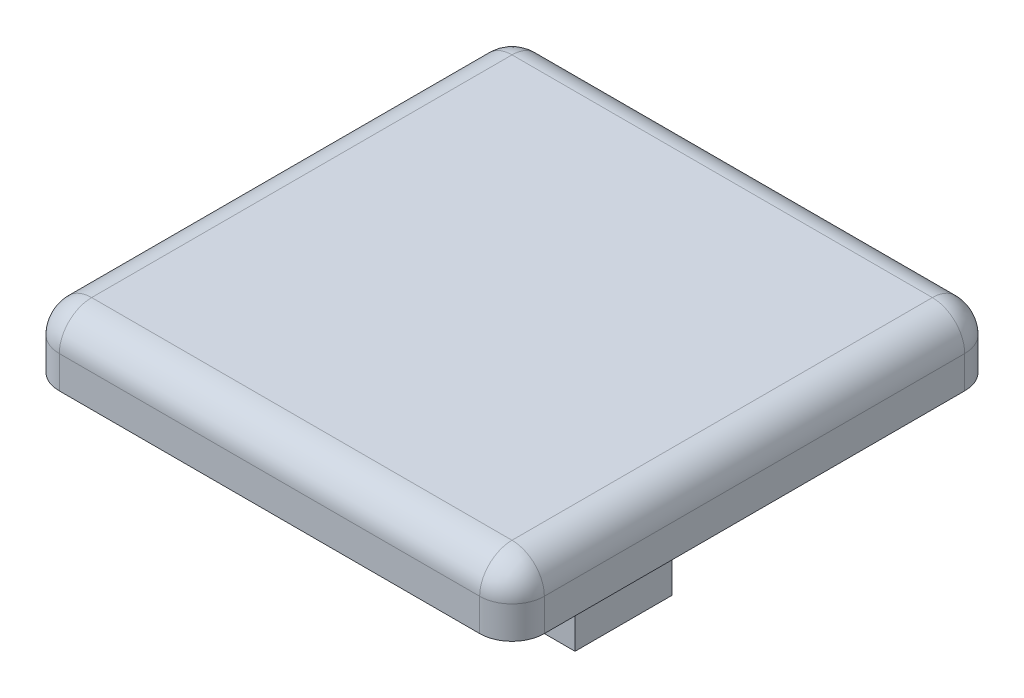
SolidWorks part; units mm, degrees
ref_plane "前视基准面" through (0, 0, 0) normal (0, 0, 1) x (1, 0, 0)
ref_plane "上视基准面" through (0, 0, 0) normal (0, 1, 0) x (1, 0, 0)
ref_plane "右视基准面" through (0, 0, 0) normal (1, 0, 0) x (0, 0, -1)
other "Configuration Table"
sketch "草图1" plane through (0, 0, 0) normal (0, 1, 0) x (1, 0, 0)
  line L0 (23.0286, 0) -> (38.0286, 0)
  line L1 (38.0286, 0) -> (38.0286, 15)
  line L2 (38.0286, 15) -> (23.0286, 15)
  line L3 (23.0286, 15) -> (23.0286, 0)
extrude "凸台-拉伸1" add sketch "草图1" along normal blind 2
fillet "圆角1" radius 1 8 edges at (30.5286, 2, 0) (38.0286, 2, -7.5) (23.0286, 2, -7.5) (30.5286, 2, -15) (38.0286, 1, -15) (23.0286, 1, -15) (38.0286, 1, 0) (23.0286, 1, 0)
sketch "草图2" plane through (0, 0, 0) normal (0, -1, 0) x (1, 0, 0)
  line L0 (28.2786, -9) -> (27.0786, -6) construction
  line L2 (32.7786, -6) -> (33.9786, -6)
  line L3 (32.7786, -6) -> (32.7786, -9)
  line L4 (32.7786, -9) -> (33.9786, -9)
  line L5 (33.9786, -6) -> (33.9786, -9)
  line L6 (32.7786, -6) -> (33.9786, -9) construction
  line L7 (32.7786, -9) -> (33.9786, -6) construction
  line L8 (28.2786, -6) -> (27.0786, -9) construction
  line L9 (27.0786, -6) -> (27.0786, -9)
  line L10 (28.2786, -9) -> (27.0786, -9)
  line L11 (28.2786, -6) -> (28.2786, -9)
  line L12 (28.2786, -6) -> (27.0786, -6)
extrude "凸台-拉伸2" add sketch "草图2" along normal blind 5
